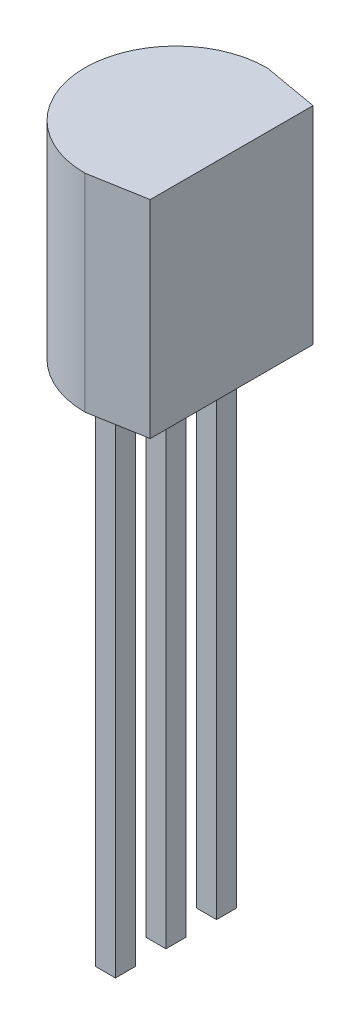
SolidWorks part; units mm, degrees
ref_plane "Front Plane" through (0, 0, 0) normal (0, 0, 1) x (1, 0, 0)
ref_plane "Top Plane" through (0, 0, 0) normal (0, 1, 0) x (1, 0, 0)
ref_plane "Right Plane" through (0, 0, 0) normal (1, 0, 0) x (0, 0, -1)
sketch "Sketch1" plane through (0, 0, 0) normal (0, 1, 0) x (1, 0, 0)
  line L0 (0.01, 2.29) -> (1.4, 2.0449)
  line L1 (0, 2.29) -> (0, -2.29)
  line L2 (0, -2.29) -> (0.01, -2.29)
  line L3 (0.01, -2.29) -> (1.4, -2.0449)
  line L4 (0, 2.29) -> (0.01, 2.29)
  line L6 (0, -2.29) -> (1.4, -2.29)
  line L7 (1.4, 2.0449) -> (1.4, -2.0449)
  arc A0 (0, 2.29) -> (0, -2.29) centre (0, 0) ccw
  point P8 (1.4, 2.29)
  dimension "D1" = 1.39
  dimension "D2" = 10
  dimension "D3" = 1.39
  dimension "D4" = 10
extrude "Boss-Extrude1" add sketch "Sketch1" along normal blind 5.2 contours L1 A0 region at (-0.9719, 0, 0)
extrude "Boss-Extrude2" add sketch "Sketch1<3>" along normal blind 5.2 contours L7 L0 L4 L1 L2 L3 region at (0.6867, 0, 0)
sketch "Sketch1<3>" plane through (0, 0, 0) normal (0, 1, 0) x (1, 0, 0) same geometry as "Sketch1"
sketch "Sketch3" plane through (0, 0, 0) normal (0, -1, 0) x (1, 0, 0)
  line L0 (-0.5, 1.27) -> (-0.5, 1.52)
  line L1 (0, 0) -> (-0.5, 0) construction
  line L2 (-0.5, 0) -> (-0.5, 0.25)
  line L3 (-0.5, 0) -> (-0.5, -0.25)
  line L4 (-0.5, -0.25) -> (0, -0.25)
  line L5 (-0.5, 1.27) -> (-0.5, 1.02)
  line L6 (-0.5, 0.25) -> (0, 0.25)
  line L7 (-0.5, 0.25) -> (-0.5, -0.25)
  line L8 (-0.5, -0.25) -> (0, -0.25)
  line L9 (0, 0.25) -> (0, -0.25)
  line L10 (-0.5, 1.02) -> (0, 1.02)
  line L11 (-0.5, 1.52) -> (0, 1.52)
  line L12 (-0.5, 1.52) -> (-0.5, 1.02)
  line L13 (-0.5, 1.02) -> (0, 1.02)
  line L14 (0, 1.52) -> (0, 1.02)
  line L15 (0, 1.27) -> (-0.5, 1.27) construction
  line L16 (-0.5, 0) -> (-0.5, 1.27) construction
  line L17 (-0.5, -1.27) -> (-0.5, -1.02)
  line L18 (-0.5, -1.27) -> (-0.5, -1.52)
  line L19 (-0.5, -1.52) -> (0, -1.52)
  line L20 (-0.5, -1.02) -> (0, -1.02)
  line L21 (-0.5, -1.02) -> (-0.5, -1.52)
  line L22 (-0.5, -1.52) -> (0, -1.52)
  line L23 (0, -1.02) -> (0, -1.52)
  line L24 (0, -1.27) -> (-0.5, -1.27) construction
  line L25 (-0.5, 0) -> (-0.5, -1.27) construction
  dimension "D1" = 1.27
  dimension "D2" = 1.27
extrude "Boss-Extrude3" add sketch "Sketch3" along normal blind 12.7 contours L23 L20 L17 L18 L19 | L9 L6 L2 L3 L4 | L14 L11 L0 L5 L10 region at (-0.25, 0, 1.27) region at (-0.25, 0, 0) region at (-0.25, 0, -1.27)
